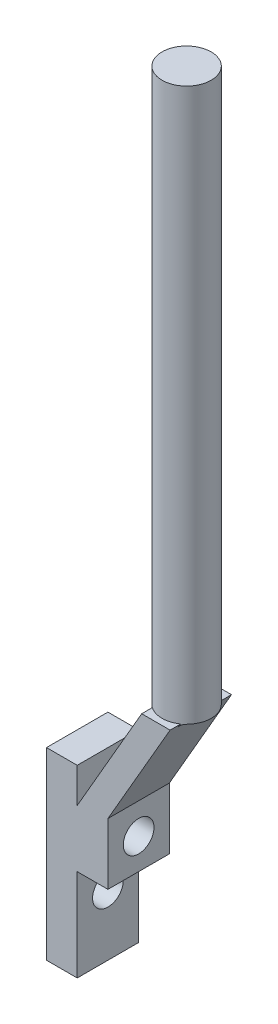
SolidWorks part; units mm, degrees
ref_plane "Plan de face" through (0, 0, 0) normal (0, 0, 1) x (1, 0, 0)
ref_plane "Plan de dessus" through (0, 0, 0) normal (0, 1, 0) x (1, 0, 0)
ref_plane "Plan de droite" through (0, 0, 0) normal (1, 0, 0) x (0, 0, -1)
sketch "Esquisse2" plane through (0, 0, 0) normal (0, 0, 1) x (1, 0, 0)
  line L0 (0, -22.3451) -> (0, 26.2264) construction
  line L1 (0, 26.2264) -> (26.2264, 0) construction
  line L2 (26.2264, 0) -> (-27.4924, 0) construction
  line L3 (-5.1895, 0) -> (11.6226, 29.1194) construction
  line L4 (-7.6895, -15) -> (-2.6895, -15)
  line L5 (-7.6895, -15) -> (-7.6895, 15)
  line L6 (-7.6895, 15) -> (-2.6895, 15)
  line L7 (-2.6895, -15) -> (-2.6895, 0)
  line L8 (-7.6895, -15) -> (-2.6895, 15) construction
  line L9 (-7.6895, 15) -> (-2.6895, -15) construction
  line L11 (-2.6895, 9.3301) -> (7.8133, 27.5215)
  line L12 (7.8133, 27.5215) -> (12.4321, 27.5215)
  line L13 (-2.6895, 9.3301) -> (-2.6895, 15)
  line L14 (-2.6895, 0) -> (2.3105, 0)
  line L15 (2.3105, 0) -> (2.3105, 9.9904)
  line L16 (2.3105, 9.9904) -> (12.4321, 27.5215)
  point P3 (-5.1895, 0)
  dimension "D1" = 5
  dimension "D2" = 30
  dimension "D3" = 60
  dimension "D4" = 5
  dimension "D5" = 4
extrude "BASE" add sketch "Esquisse2" along normal blind 10
sketch "Esquisse3" plane through (-7.6895, 0, 0) normal (-1, 0, 0) x (0, 0, 1)
  line L0 (0, -15) -> (10, 15) construction
  line L1 (10, 15) -> (5, 15) construction
  line L2 (10, 15) -> (0, 15) construction
  line L3 (5, 15) -> (5, -15) construction
  line L4 (10, -15) -> (0, -15) construction
  circle A0 centre (5, 5) radius 2.5
  circle A1 centre (5, -5) radius 2.5
  point P14 (5, 0)
  dimension "D1" = 5
  dimension "D2" = 5
  dimension "D3" = 10
  dimension "D4" = 5
extrude "VIDE TROU" cut sketch "Esquisse3" against normal blind 10
sketch "Esquisse4" plane through (0, 27.5215, 0) normal (0, 1, 0) x (1, 0, 0)
  line L0 (12.4321, 0) -> (7.8133, -10) construction
  line L1 (7.8133, -10) -> (7.8133, 0) construction
  line L2 (7.8133, 0) -> (12.4321, -10) construction
  circle A0 centre (10.1227, -5) radius 4
  dimension "D1" = 8
extrude "AXE" add sketch "Esquisse4" along normal blind 90
fillet "Congé5" radius 1 2 edges at (7.8133, 27.5215, 5) (12.4321, 27.5215, 5)
